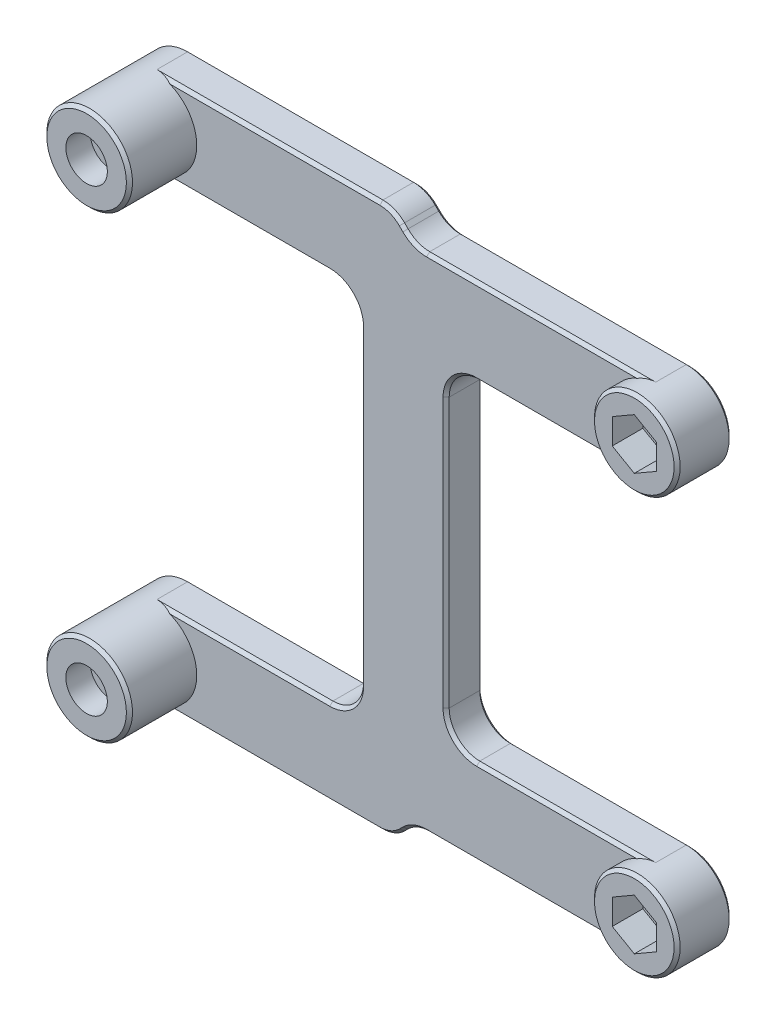
SolidWorks part; units mm, degrees
ref_plane "Front Plane" through (0, 0, 0) normal (0, 0, 1) x (1, 0, 0)
ref_plane "Top Plane" through (0, 0, 0) normal (0, 1, 0) x (1, 0, 0)
ref_plane "Right Plane" through (0, 0, 0) normal (1, 0, 0) x (0, 0, -1)
sketch "Sketch1" plane through (0, 0, 0) normal (0, 0, 1) x (1, 0, 0)
  line L114 (0, 82) -> (36.9289, 82)
  line L118 (0, 68) -> (28.75, 68)
  line L120 (81.5, 64.5) -> (52.75, 64.5)
  line L122 (81.5, 78.5) -> (44.5711, 78.5)
  line L123 (81.5, 10.5) -> (52.75, 10.5)
  line L124 (81.5, -3.5) -> (44.5711, -3.5)
  line L125 (0, -7) -> (36.9289, -7)
  line L126 (0, 7) -> (28.75, 7)
  line L128 (33.75, 63) -> (33.75, 12)
  line L129 (47.75, 15.5) -> (47.75, 59.5)
  line L131 (41.0355, -4.9645) -> (40.4645, -5.5355)
  line L133 (40.4645, 80.5355) -> (41.0355, 79.9645)
  circle A33 centre (0, 0) radius 4.5
  circle A57 centre (0, 75) radius 4.5
  circle A78 centre (81.5, 71.5) radius 2.15
  circle A80 centre (81.5, 3.5) radius 2.15
  arc A90 (0, 7) -> (0, -7) centre (0, 0) ccw
  arc A91 (0, 82) -> (0, 68) centre (0, 75) ccw
  arc A92 (81.5, 64.5) -> (81.5, 78.5) centre (81.5, 71.5) ccw
  arc A93 (81.5, -3.5) -> (81.5, 10.5) centre (81.5, 3.5) ccw
  arc A110 (40.4645, -5.5355) -> (36.9289, -7) centre (36.9289, -2) cw
  arc A111 (44.5711, -3.5) -> (41.0355, -4.9645) centre (44.5711, -8.5) ccw
  arc A112 (47.75, 15.5) -> (52.75, 10.5) centre (52.75, 15.5) ccw
  arc A113 (33.75, 12) -> (28.75, 7) centre (28.75, 12) cw
  arc A114 (47.75, 59.5) -> (52.75, 64.5) centre (52.75, 59.5) cw
  arc A115 (33.75, 63) -> (28.75, 68) centre (28.75, 63) ccw
  arc A116 (41.0355, 79.9645) -> (44.5711, 78.5) centre (44.5711, 83.5) ccw
  arc A117 (36.9289, 82) -> (40.4645, 80.5355) centre (36.9289, 77) cw
extrude "Boss-Extrude1" add sketch "Sketch1" along normal blind 6
sketch "Sketch2" plane through (0, 0, 6) normal (0, 0, 1) x (1, 0, 0)
  circle A1 centre (0, 75) radius 3.39
  circle A2 centre (0, 0) radius 3.39
  circle A4 centre (0, 0) radius 7
  circle A5 centre (0, 75) radius 7
extrude "Boss-Extrude2" add sketch "Sketch2" along normal blind 12.5 from offset 1.5 offset against normal yes
sketch "Sketch3" plane through (0, 0, 0) normal (0, 0, -1) x (-1, 0, 0)
  circle A0 centre (0, 75) radius 3.5
  circle A1 centre (0, 75) radius 1.65
  circle A2 centre (0, 0) radius 3.5
  circle A3 centre (0, 0) radius 1.65
extrude "Boss-Extrude3" add sketch "Sketch3" against normal offset from surface (8.5 mm away) 4 from surface up to face at (7, 0, 17) starting at face at (3.39, 0, 4.5)
sketch "Sketch6" plane through (0, 0, 6) normal (0, 0, 1) x (1, 0, 0)
  circle A0 centre (81.5, 3.5) radius 7
  circle A1 centre (81.5, 3.5) radius 2.15
  circle A2 centre (81.5, 71.5) radius 2.15
  circle A3 centre (81.5, 71.5) radius 7
extrude "Boss-Extrude4" add sketch "Sketch6" along normal blind 3
sketch "Sketch5" plane through (0, 0, 9) normal (0, 0, 1) x (1, 0, 0)
  line L0 (77.9, 5.5785) -> (81.5, 7.6569)
  line L1 (77.9, 1.4215) -> (77.9, 5.5785)
  line L2 (81.5, -0.6569) -> (77.9, 1.4215)
  line L3 (85.1, 1.4215) -> (81.5, -0.6569)
  line L4 (85.1, 5.5785) -> (85.1, 1.4215)
  line L5 (81.5, 7.6569) -> (85.1, 5.5785)
  line L7 (77.9, 73.5785) -> (81.5, 75.6569)
  line L8 (77.9, 69.4215) -> (77.9, 73.5785)
  line L9 (81.5, 67.3431) -> (77.9, 69.4215)
  line L10 (85.1, 69.4215) -> (81.5, 67.3431)
  line L11 (85.1, 73.5785) -> (85.1, 69.4215)
  line L12 (81.5, 75.6569) -> (85.1, 73.5785)
extrude "Cut-Extrude1" cut sketch "Sketch5" against normal blind 5
chamfer "Chamfer1" distance 0.5 angle 45 48 edges at (32.2855, 8.4645, 0) (88.5, 3.5, 0) (49.2145, 11.9645, 0) (-7, 0, 0) (42.6577, -3.8806, 0) (88.5, 71.5, 0) (40.75, 80.25, 0) (-7, 75, 0) (40.75, 80.25, 6) (32.2855, 8.4645, 6) (49.2145, 11.9645, 6) (42.6577, -3.8806, 6) (18.4645, 82, 6) (38.8423, 81.6194, 6) (42.6577, 78.8806, 6) (63.0355, 78.5, 6) (88.5, 71.5, 9) (88.5, 3.5, 9) (67.125, 64.5, 6) (49.2145, 63.0355, 6) (47.75, 37.5, 6) (67.125, 10.5, 6) (63.0355, -3.5, 6) (40.75, -5.25, 6) (38.8423, -6.6194, 6) (18.4645, -7, 6) (14.375, 68, 6) (32.2855, 66.5355, 6) (33.75, 37.5, 6) (14.375, 7, 6) (7, 0, 17) (7, 75, 17) (63.0355, -3.5, 0) (67.125, 10.5, 0) (40.75, -5.25, 0) (38.8423, -6.6194, 0) (47.75, 37.5, 0) (18.4645, -7, 0) (49.2145, 63.0355, 0) (67.125, 64.5, 0) (14.375, 7, 0) (63.0355, 78.5, 0) (33.75, 37.5, 0) (42.6577, 78.8806, 0) (32.2855, 66.5355, 0) (14.375, 68, 0) (38.8423, 81.6194, 0) (18.4645, 82, 0)
